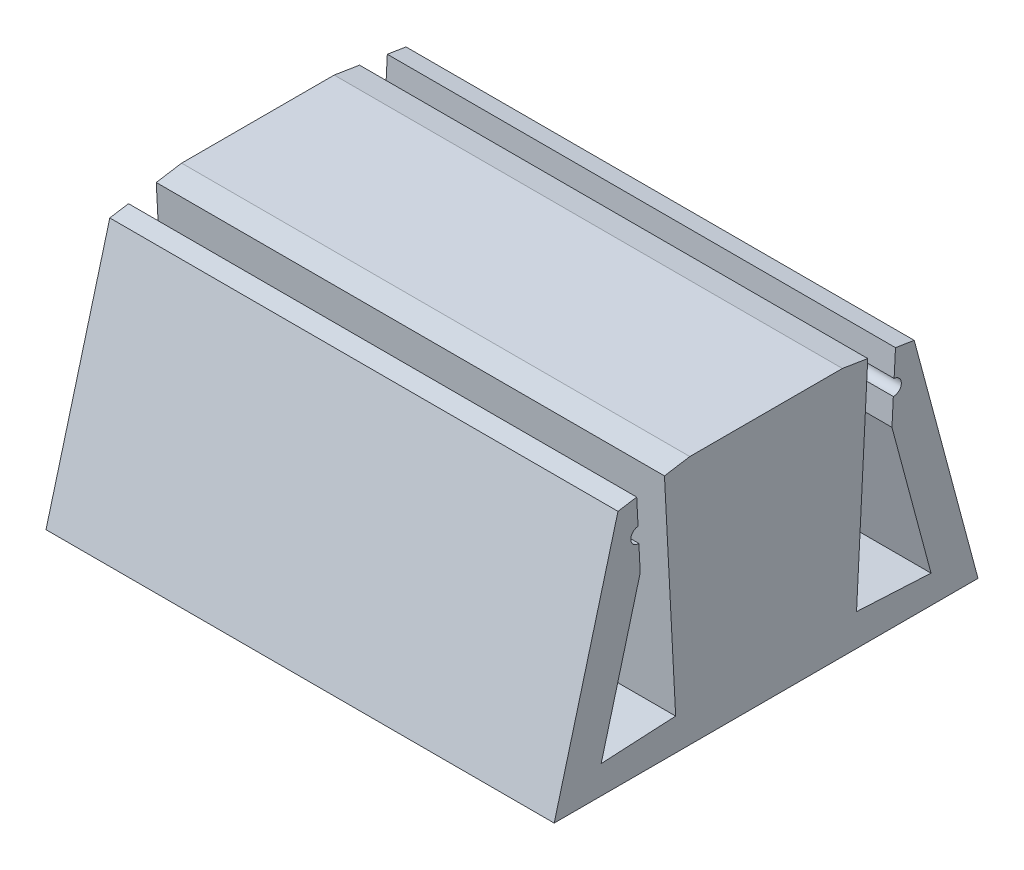
SolidWorks part; units mm, degrees
ref_plane "Front Plane" through (0, 0, 0) normal (0, 0, 1) x (1, 0, 0)
ref_plane "Top Plane" through (0, 0, 0) normal (0, 1, 0) x (1, 0, 0)
ref_plane "Right Plane" through (0, 0, 0) normal (1, 0, 0) x (0, 0, -1)
sketch "Sketch1" plane through (0, 0, 0) normal (1, 0, 0) x (0, 0, -1)
  line L0 (3.6311, 0.3059) -> (9.4677, 0) construction
  line L1 (3.904, 5.5131) -> (4.9077, 5.4605) construction
  line L2 (6.2203, 9.4885) -> (6.0816, 6.8415) construction
  line L3 (6.0816, 6.8415) -> (7.6191, 1.1033)
  line L4 (7.6191, 1.1033) -> (4.6874, 1.2569)
  line L5 (4.6874, 1.2569) -> (5.128, 9.664)
  line L6 (5.128, 9.664) -> (4.13, 9.8243)
  line L7 (4.13, 9.8243) -> (3.6311, 0.3059) construction
  line L8 (6.2203, 9.4885) -> (6.1666, 8.4646)
  line L9 (6.1352, 7.8654) -> (6.0816, 6.8415)
  line L10 (6.2203, 9.4885) -> (6.9569, 9.3702)
  line L11 (6.9569, 9.3702) -> (9.4677, 0)
  line L12 (6.1532, 1.1801) -> (6.1006, 0.1765) construction
  line L13 (1.128, 0) -> (1.128, 7.6812) construction
  line L14 (-3.8973, 1.1801) -> (-3.8447, 0.1765) construction
  line L15 (-5.3632, 1.1033) -> (-2.4314, 1.2569)
  line L16 (-3.9644, 9.4885) -> (-3.8256, 6.8415) construction
  line L17 (-1.6481, 5.5131) -> (-2.6517, 5.4605) construction
  line L18 (-1.3752, 0.3059) -> (-7.2117, 0) construction
  line L19 (-4.701, 9.3702) -> (-7.2117, 0)
  line L20 (-3.9644, 9.4885) -> (-4.701, 9.3702)
  line L21 (-3.8793, 7.8654) -> (-3.8256, 6.8415)
  line L22 (-3.9644, 9.4885) -> (-3.9107, 8.4646)
  line L23 (-1.874, 9.8243) -> (-1.3752, 0.3059) construction
  line L24 (-2.872, 9.664) -> (-1.874, 9.8243)
  line L25 (-2.4314, 1.2569) -> (-2.872, 9.664)
  line L26 (-3.8256, 6.8415) -> (-5.3632, 1.1033)
  line L27 (-1.874, 9.8243) -> (4.13, 9.8243)
  line L28 (-7.2117, 0) -> (-2.3656, 0)
  line L29 (-2.4314, 1.2569) -> (-2.3656, 0)
  line L30 (4.6874, 1.2569) -> (4.6215, 0)
  line L31 (-2.3656, 0) -> (4.6215, 0)
  line L32 (4.6215, 0) -> (9.4677, 0)
  arc A0 (6.1666, 8.4646) -> (6.1352, 7.8654) centre (6.1509, 8.165) cw
  arc A1 (-3.9107, 8.4646) -> (-3.8793, 7.8654) centre (-3.895, 8.165) ccw
  point P37 (0, 0)
  dimension "D1" = 0.3
  dimension "D2" = 1.1
  dimension "D3" = 72
  dimension "D4" = 1.5
  dimension "D5" = 8
extrude "Boss-Extrude1" add sketch "Sketch1" along normal mid plane 20 contours L28 L19 L20 L22 A1 L21 L26 L15 L25 L24 L27 L6 L5 L4 L3 L9 A0 L8 L10 L11 L32 L31
